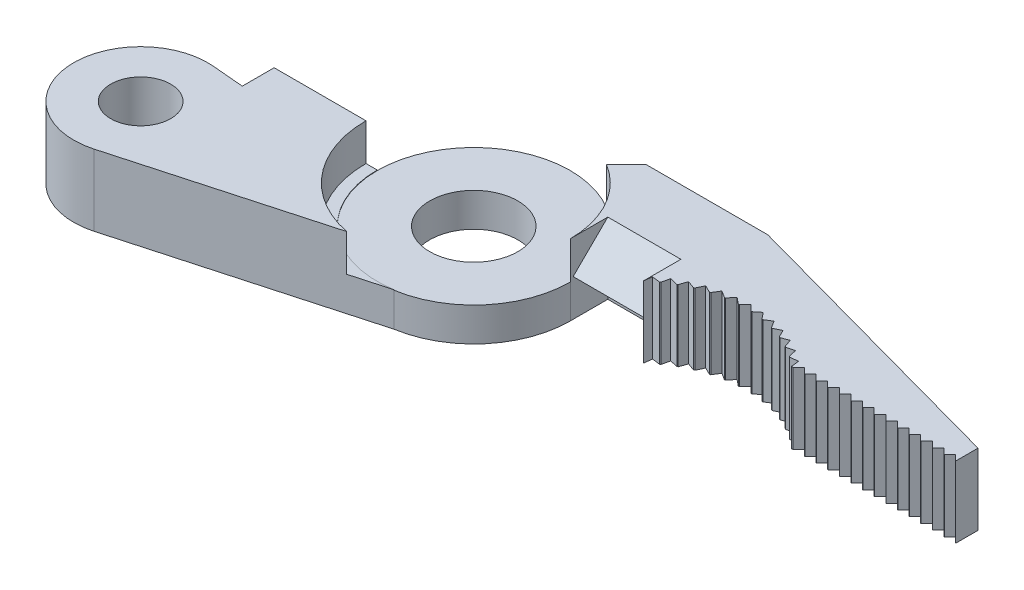
SolidWorks part; units mm, degrees
ref_plane "Front Plane" through (0, 0, 0) normal (0, 0, 1) x (1, 0, 0)
ref_plane "Top Plane" through (0, 0, 0) normal (0, 1, 0) x (1, 0, 0)
ref_plane "Right Plane" through (0, 0, 0) normal (1, 0, 0) x (0, 0, -1)
sketch "Sketch1" plane through (0, 0, 0) normal (0, 1, 0) x (1, 0, 0)
  circle A0 centre (0, 0) radius 6.5405
  circle A1 centre (0, 0) radius 2.9845
  dimension "D1" = 13.081
  dimension "D2" = 5.969
extrude "Boss-Extrude1" add sketch "Sketch1" along normal blind 4.826
sketch "Sketch2" plane through (0, 0, 0) normal (0, 1, 0) x (1, 0, 0)
  line L0 (-6.5405, 0) -> (-13.5255, 0)
  line L1 (-13.5255, 0) -> (-13.5255, -2.159)
  line L2 (-15.6763, -1.9708) -> (-13.5255, -2.159)
  line L3 (1.0584, -6.4543) -> (-14.8567, -10.8736)
  circle A1 centre (-16.0722, -6.4964) radius 2.032
  circle A2 centre (0, 0) radius 2.9845 construction
  arc A3 (-15.6763, -1.9708) -> (-14.8567, -10.8736) centre (-16.0722, -6.4964) ccw
  arc A4 (-6.5405, 0) -> (1.0584, -6.4543) centre (0, 0) ccw
  dimension "D1" = 4.064
  dimension "D6" = 17.3355
  dimension "D2" = 6.985
  dimension "D3" = 2.159
  dimension "D4" = 2.159
  dimension "D5" = 85
extrude "Boss-Extrude2" add sketch "Sketch2" along normal up to surface (4.826 mm away) up to face at (0, 4.826, 6.5405)
hole_wizard "#43 (0.089) Diameter Hole1" positions "Sketch6" profile "Sketch7" hole size "#43" standard "ANSI Inch"
sketch "Sketch6" plane through (0, 0, 0) normal (0, 0, -1) x (-1, 0, 0)
  line L0 (13.5255, 4.826) -> (13.5255, 0) construction
  line L1 (6.5405, 0) -> (13.5255, 0) construction
  point P0 (10.033, 2.413)
  dimension "D1" = 3.4925
  dimension "D2" = 2.413
sketch "Sketch7" plane through (-10.033, 2.413, 0) normal (1, 0, 0) x (0, 1, 0)
  line L0 (0, 0) -> (0, 2.7112)
  line L1 (0, 2.7112) -> (1.1303, 2.032)
  line L2 (1.1303, 2.032) -> (1.1303, 0)
  line L5 (1.1303, 0) -> (0, 0)
  line L10 (0, 2.7112) -> (-1.1303, 2.032) construction
  line L11 (0, -6.35) -> (0, 107.95) construction
  dimension "Hole Dia." = 2.2606
  dimension "Hole Depth" = 2.032
  dimension "Drill Angle" = 118
sketch "Sketch8" plane through (0, 0, 0) normal (0, 1, 0) x (1, 0, 0)
  line L0 (13.0016, 6.9215) -> (32.639, 1.524)
  line L1 (32.639, 1.524) -> (32.639, 0)
  line L2 (32.639, 0) -> (21.5265, 0)
  line L3 (13.0016, 6.9215) -> (4.7466, 6.9215)
  line L4 (4.7466, 6.9215) -> (3.4077, 5.5826)
  line L5 (6.5405, 0) -> (11.4935, 0)
  arc A2 (1.0584, -6.4543) -> (-6.5405, 0) centre (0, 0) ccw construction
  arc A4 (21.5265, 0) -> (11.4935, 0) centre (16.51, -5.7358) ccw
  arc A5 (6.5405, 0) -> (3.4077, 5.5826) centre (0, 0) ccw
  dimension "D1" = 0.381
  dimension "D8" = 15.24
  dimension "D2" = 1.524
  dimension "D3" = 8.255
  dimension "D4" = 32.639
  dimension "D5" = 225
  dimension "D6" = 11.1125
  dimension "D7" = 4.953
extrude "Boss-Extrude3" add sketch "Sketch8" along normal up to surface (4.826 mm away) up to face at (-10.2367, 4.826, 2.2894)
sketch "Sketch9" plane through (0, 4.826, 0) normal (0, 1, 0) x (1, 0, 0)
  line L10 (-7.3025, 0) -> (-6.5405, 0)
  line L11 (-1.463, -7.1544) -> (1.0584, -6.4543)
  line L12 (-14.8567, -10.8736) -> (1.0584, -6.4543) construction
  line L32 (33.401, -0.762) -> (33.401, 2.1048)
  arc A4 (-7.3025, 0) -> (-1.463, -7.1544) centre (0, 0) ccw
  arc A5 (-6.5405, 0) -> (1.0584, -6.4543) centre (0, 0) ccw
  arc A6 (3.4077, 5.5826) -> (-6.5405, 0) centre (0, 0) ccw construction
  arc A7 (1.0584, -6.4543) -> (6.5405, 0) centre (0, 0) ccw construction
  line M26 (-6.5405, 0) -> (-13.5255, 0)
  line M30 (-14.8567, -10.8736) -> (1.0584, -6.4543)
  dimension "D1" = 0.762
  dimension "D2" = 6.5405
  dimension "D3" = 2.6168
extrude "Cut-Extrude1" cut sketch "Sketch9" against normal blind 2.5082 contours A5 A4 M26 M30 region at (-6.9215, 4.826, 0.11)
sketch "Sketch10" plane through (0, 4.826, 0) normal (0, 1, 0) x (1, 0, 0)
  line L0 (32.639, 0) -> (32.258, 0.381)
  line L1 (32.258, 0.381) -> (31.877, 0)
  line L3 (21.5265, 0) -> (32.639, 0) construction
  line L4 (31.877, 0) -> (32.639, 0)
  dimension "D1" = 0.381
extrude "Cut-Extrude2" cut sketch "Sketch10" against normal through all
pattern_linear "LPattern1" count 14 spacing 0.7874 along (-1, 0, 0) of "Cut-Extrude2"
sketch "Sketch11" plane through (0, 4.826, 0) normal (0, 1, 0) x (1, 0, 0)
  line L0 (21.5265, 0) -> (21.4646, 0.5466)
  line L1 (21.4646, 0.5466) -> (20.9187, 0.4794)
  arc A0 (21.5265, 0) -> (11.4935, 0) centre (16.51, -5.7358) ccw construction
  arc A1 (21.5265, 0) -> (20.9187, 0.4794) centre (16.51, -5.7358) ccw
  dimension "D1" = 8.001
extrude "Cut-Extrude3" cut sketch "Sketch11" against normal through all
pattern_circular "CirPattern1" count 13 over 76.5 about axis through (16.51, 4.826, 5.7358) along (0, -1, 0) of "Cut-Extrude3" reverse direction yes
sketch "Sketch13" plane through (0, 4.826, 0) normal (0, 1, 0) x (1, 0, 0)
  line L0 (11.4935, 0) -> (11.4935, 2.54)
  line L1 (11.4935, 2.54) -> (6.5405, 2.54)
  line L2 (6.5405, 2.54) -> (6.5405, 0)
  line L3 (6.5405, 0) -> (11.4935, 0)
  dimension "D1" = 2.54
extrude "Cut-Extrude5" cut sketch "Sketch13" against normal blind 2.5082
sketch "Sketch14" plane through (6.5405, 0, 0) normal (1, 0, 0) x (0, 0, -1)
  line L0 (0, 2.3178) -> (2.54, 4.826)
  line L1 (2.54, 4.826) -> (2.54, 2.3177)
  line L2 (2.54, 2.3177) -> (2.54, 4.826) construction
  line L3 (2.54, 2.3177) -> (0, 2.3178) construction
  line L4 (2.54, 2.3177) -> (0, 2.3178)
extrude "Boss-Extrude4" add sketch "Sketch14" along normal up to next
sketch "Sketch15" plane through (0, 0, 0) normal (0, -1, 0) x (1, 0, 0)
  line L0 (6.5405, 0) -> (6.5405, -2.54)
  line L1 (6.5405, 0) -> (11.4935, 0) construction
  line L2 (6.5405, -2.54) -> (11.52, -2.54)
  line L3 (11.52, -2.54) -> (11.4935, 0)
  line L4 (11.4935, 0) -> (6.5405, 0)
  arc A0 (6.5405, 0) -> (1.0584, 6.4543) centre (0, 0) ccw construction
  dimension "D1" = 2.54
extrude "Cut-Extrude6" cut sketch "Sketch15" against normal blind 2.5082
sketch "Sketch16" plane through (0, 4.826, 0) normal (0, 1, 0) x (1, 0, 0)
  circle A0 centre (0, 0) radius 6.5405
extrude "Cut-Extrude7" cut sketch "Sketch16" against normal blind 2.54
